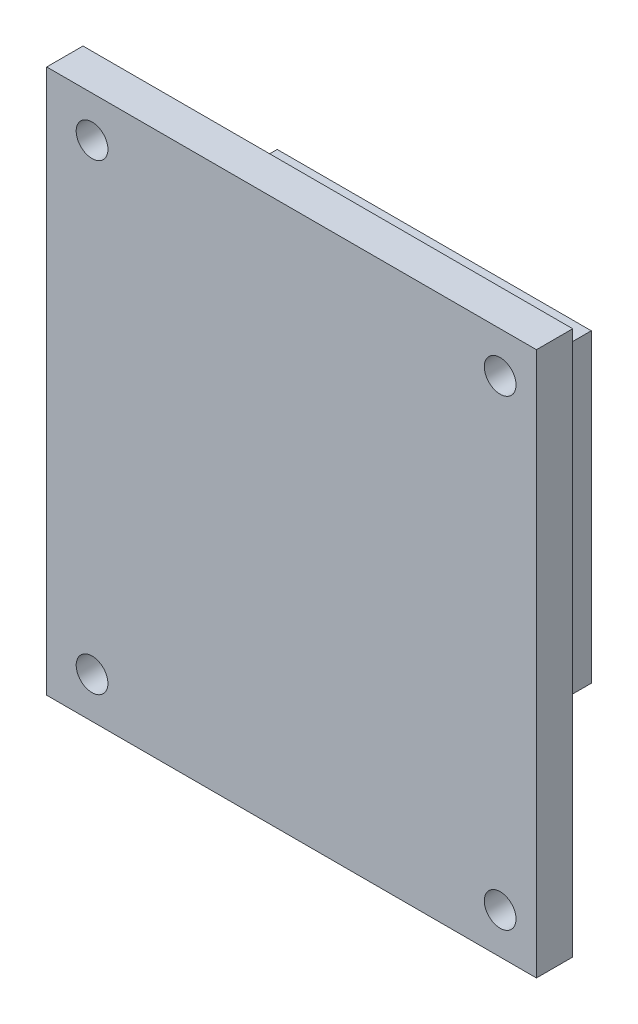
SolidWorks part; units mm, degrees
ref_plane "Plan de face" through (0, 0, 0) normal (0, 0, 1) x (1, 0, 0)
ref_plane "Plan de dessus" through (0, 0, 0) normal (0, 1, 0) x (1, 0, 0)
ref_plane "Plan de droite" through (0, 0, 0) normal (1, 0, 0) x (0, 0, -1)
sketch "Esquisse1" plane through (0, 0, 0) normal (0, 0, 1) x (1, 0, 0)
  line L1 (0, 0) -> (54, 0)
  line L2 (0, 0) -> (0, -60)
  line L3 (0, -60) -> (54, -60)
  line L4 (54, 0) -> (54, -60)
  line L6 (54, 0) -> (54, -60)
  circle A3 centre (5, -55.5) radius 1.75
  circle A4 centre (50, -55.5) radius 1.75
  circle A5 centre (50, -4.5) radius 1.75
  circle A6 centre (5, -4.5) radius 1.75
  point P24 (0, 0)
  dimension "D14" = 3.5
  dimension "D19" = 3.5
  dimension "D20" = 3.5
  dimension "D21" = 3.5
  dimension "D22" = 5
  dimension "D4" = 60
  dimension "D5" = 54
  dimension "D15" = 51
  dimension "D16" = 51
  dimension "D17" = 45
  dimension "D18" = 45
  dimension "D23" = 4.5
  dimension "D24" = 4.5
  dimension "D25" = 4.5
  dimension "D26" = 4.5
extrude "Boss.-Extru.1" add sketch "Esquisse1" along normal blind 4 contours L4 L1 L2 L3 | L4 region at (26.994, -30, 0)
sketch "Esquisse2" plane through (0, 0, 0) normal (0, 0, -1) x (-1, 0, 0)
  line L1 (-7.4156, -46.8316) -> (-42.0485, -46.8316)
  line L2 (-7.4156, -46.8316) -> (-7.4156, -28.8316)
  line L3 (-7.4156, -28.8316) -> (-42.0485, -28.8316)
  line L4 (-42.0485, -46.8316) -> (-42.0485, -28.8316)
  dimension "D1" = 18
extrude "Boss.-Extru.3" add sketch "Esquisse2" along normal blind 14
sketch "Esquisse3" plane through (42.0485, 0, 0) normal (1, 0, 0) x (0, 0, -1)
  line L0 (0, 0) -> (0, -60) construction
  line L1 (10, -42.8316) -> (0, -42.8316)
  line L2 (10, -42.8316) -> (10, -32.8316)
  line L3 (10, -32.8316) -> (0, -32.8316)
  line L4 (0, -42.8316) -> (0, -32.8316)
  line L5 (14, -46.8316) -> (0, -46.8316) construction
  dimension "D1" = 10
  dimension "D2" = 10
  dimension "D3" = 0
  dimension "D4" = 4
extrude "Enlèv. mat.-Extru.3" cut sketch "Esquisse3" against normal through all
ref_plane "Plan1" through (0, -30, 0) normal (0, -1, 0) x (-1, 0, 0)
mirror "Symétrie1" about plane through (0, -30, 0) normal (0, -1, 0) of "Boss.-Extru.3", "Enlèv. mat.-Extru.3"
sketch "Esquisse4" plane through (0, -46.8316, 0) normal (0, -1, 0) x (1, 0, 0)
  line L0 (42.0485, -14) -> (7.4156, -14) construction
  circle A0 centre (11.4275, -10) radius 2
  point P2 (0, 0)
  dimension "D1" = 4
extrude "Enlèv. mat.-Extru.4" cut sketch "Esquisse4" against normal blind 42
equation "\"é\"=1.5583"
